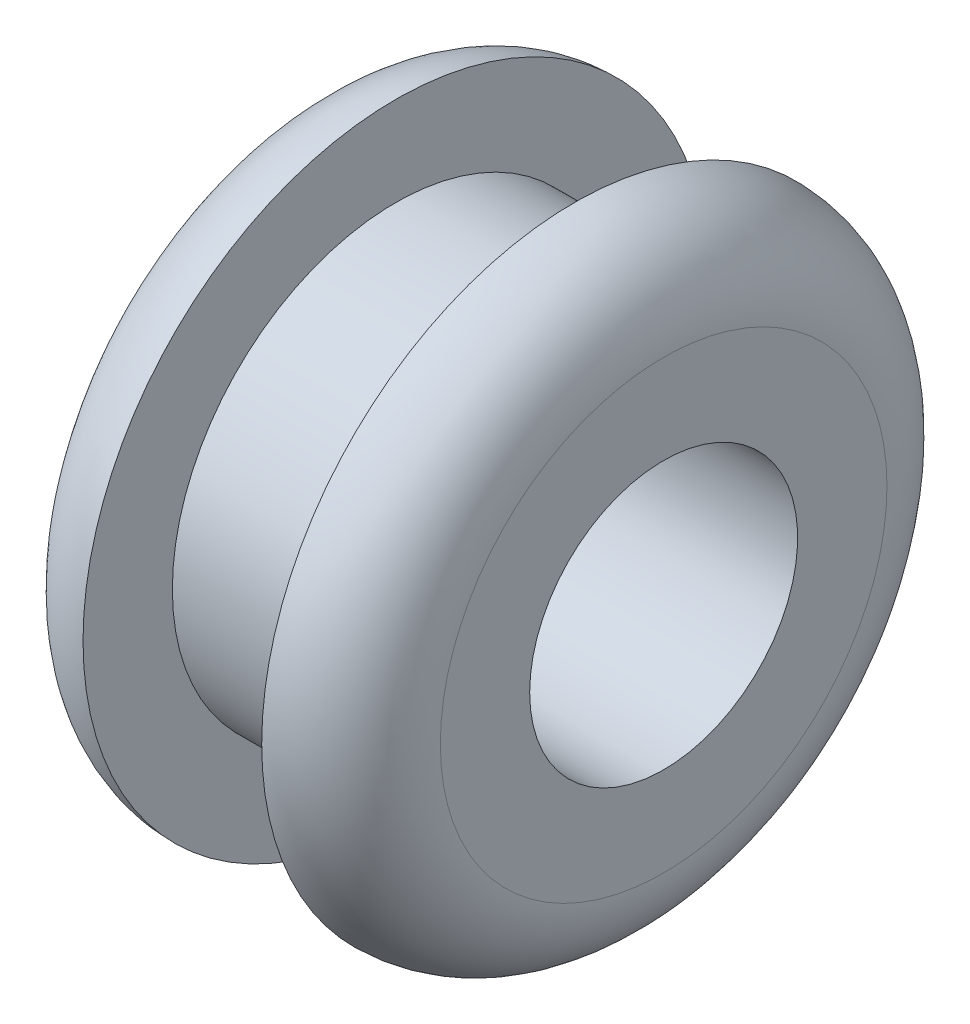
SolidWorks part; units mm, degrees
material "AISI 304"
ref_plane "XY Plane" through (0, 0, 0) normal (0, 0, 1) x (1, 0, 0)
ref_plane "XZ Plane" through (0, 0, 0) normal (0, 1, 0) x (1, 0, 0)
ref_plane "YZ Plane" through (0, 0, 0) normal (1, 0, 0) x (0, 0, -1)
ref_axis "X axis" through (-32.3056, 0, 0) along (1, 0, 0)
ref_axis "Y axis" through (0, 32.3056, 0) along (0, -1, 0)
ref_axis "Z axis" through (0, 0, 5.334) along (0, 0, -1)
sketch "Sketch1" plane through (0, 0, 0) normal (0, 0, 1) x (1, 0, 0)
  line L0 (-4.9117, 0) -> (4.9117, 0) construction
  line L1 (0, 0) -> (0, 7.125) construction
  line L2 (-3.175, 2.3813) -> (3.175, 2.3813)
  line L3 (3.175, 2.3813) -> (3.175, 3.9688)
  line L4 (1.5875, 5.5562) -> (1.5875, 3.9688)
  line L5 (1.5875, 3.9688) -> (-1.5875, 3.9688)
  line L6 (-1.5875, 5.5562) -> (-1.5875, 3.9688)
  line L7 (-3.175, 2.3813) -> (-3.175, 3.9688)
  arc A0 (3.175, 3.9688) -> (1.5875, 5.5562) centre (1.5875, 3.9688) ccw
  arc A1 (-3.175, 3.9688) -> (-1.5875, 5.5562) centre (-1.5875, 3.9688) cw
  point P17 (0, 3.9688)
  point P18 (0, 2.3813)
  dimension "D1" = 3.175
  dimension "D2" = 4.7625
  dimension "D3" = 6.35
  dimension "D4" = 7.9375
  dimension "D5" = 11.1125
revolve "Revolve1" add sketch "Sketch1" angle 360 about L0
